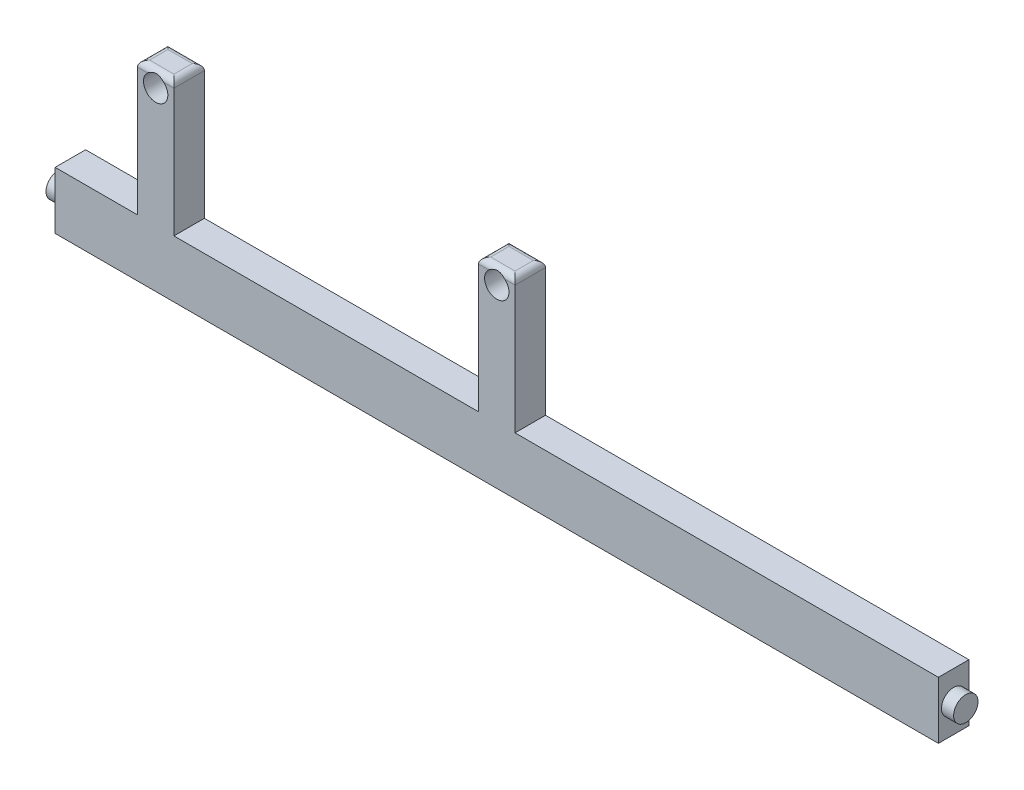
SolidWorks part; units mm, degrees
material "Chrome Stainless Steel"
ref_plane "Front Plane" through (0, 0, 0) normal (0, 0, 1) x (1, 0, 0)
ref_plane "Top Plane" through (0, 0, 0) normal (0, 1, 0) x (1, 0, 0)
ref_plane "Right Plane" through (0, 0, 0) normal (1, 0, 0) x (0, 0, -1)
sketch "Sketch1" plane through (0, 0, 0) normal (0, 0, 1) x (1, 0, 0)
  line L0 (-76.447, -6.4931) -> (-76.447, 87.5069)
  line L1 (-76.447, 87.5069) -> (58.553, 87.5069)
  line L2 (58.553, 87.5069) -> (58.553, 307.5069)
  line L3 (58.553, 307.5069) -> (118.553, 307.5069)
  line L4 (118.553, 307.5069) -> (118.553, 87.5069)
  line L5 (118.553, 87.5069) -> (618.553, 87.5069)
  line L6 (618.553, 87.5069) -> (618.553, 307.5069)
  line L7 (618.553, 307.5069) -> (678.553, 307.5069)
  line L8 (678.553, 307.5069) -> (678.553, 87.5069)
  line L9 (678.553, 87.5069) -> (1373.553, 87.5069)
  line L10 (1373.553, 87.5069) -> (1373.553, -6.4931)
  line L11 (1373.553, -6.4931) -> (-76.447, -6.4931)
  dimension "D1" = 94
  dimension "D2" = 135
  dimension "D3" = 220
  dimension "D4" = 60
  dimension "D5" = 220
  dimension "D6" = 500
  dimension "D7" = 220
  dimension "D8" = 60
  dimension "D9" = 220
  dimension "D10" = 695
extrude "Boss-Extrude1" add sketch "Sketch1" along normal blind 50
sketch "Sketch2" plane through (-76.447, 0, 0) normal (-1, 0, 0) x (0, 0, 1)
  circle A0 centre (25, 40.5069) radius 20
extrude "Boss-Extrude2" add sketch "Sketch2" along normal blind 20
sketch "Sketch3" plane through (1373.553, 0, 0) normal (1, 0, 0) x (0, 0, -1)
  circle A0 centre (-25, 40.5069) radius 20
extrude "Boss-Extrude3" add sketch "Sketch3" along normal blind 20
sketch "Sketch4" plane through (0, 0, 50) normal (0, 0, 1) x (1, 0, 0)
  line L0 (118.553, 307.5069) -> (58.553, 307.5069) construction
  circle A0 centre (88.553, 282.5069) radius 20
  point P4 (88.553, 307.5069)
  dimension "D1" = 25
extrude "Cut-Extrude1" cut sketch "Sketch4" against normal blind 70
sketch "Sketch5" plane through (0, 0, 50) normal (0, 0, 1) x (1, 0, 0)
  line L0 (678.553, 307.5069) -> (618.553, 307.5069) construction
  circle A0 centre (648.553, 282.5069) radius 20
  dimension "D1" = 25
extrude "Cut-Extrude2" cut sketch "Sketch5" against normal blind 70
fillet "Fillet1" radius 10 8 edges at (678.553, 307.5069, 25) (648.553, 307.5069, 50) (618.553, 307.5069, 25) (648.553, 307.5069, 0) (118.553, 307.5069, 25) (88.553, 307.5069, 50) (58.553, 307.5069, 25) (88.553, 307.5069, 0)
